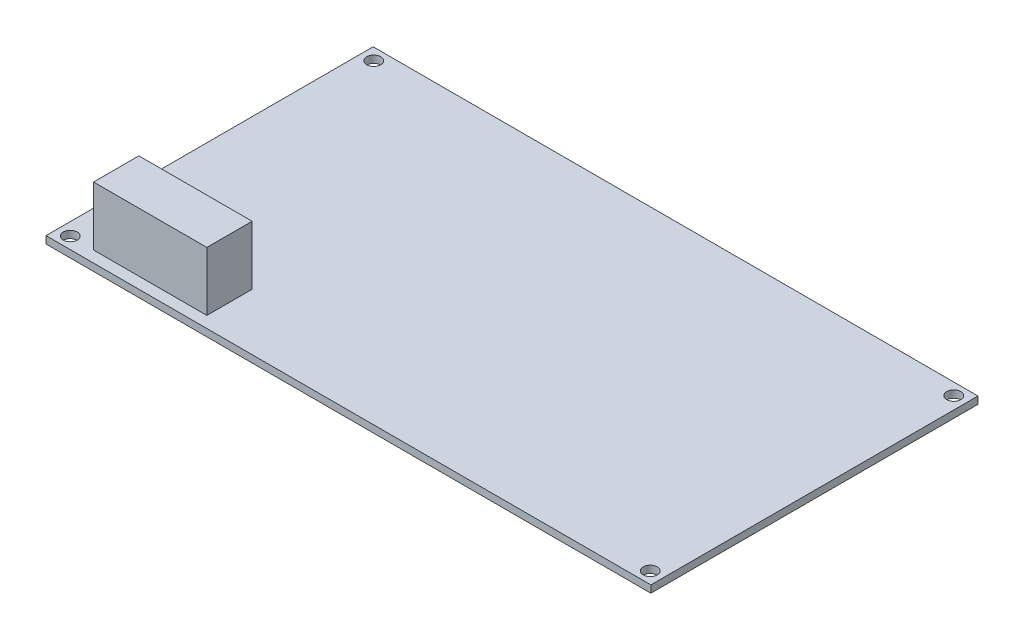
SolidWorks part; units mm, degrees
ref_plane "Front Plane" through (0, 0, 0) normal (0, 0, 1) x (1, 0, 0)
ref_plane "Top Plane" through (0, 0, 0) normal (0, 1, 0) x (1, 0, 0)
ref_plane "Right Plane" through (0, 0, 0) normal (1, 0, 0) x (0, 0, -1)
sketch "Sketch1" plane through (0, 0, 0) normal (0, 1, 0) x (1, 0, 0)
  line L0 (66.75, 72.2) -> (66.75, 69.6) construction
  line L1 (0, 0) -> (133.5, 0)
  line L2 (0, 0) -> (0, 72.2)
  line L3 (0, 72.2) -> (133.5, 72.2)
  line L4 (133.5, 0) -> (133.5, 72.2)
  line L5 (2.75, 69.6) -> (130.75, 69.6) construction
  line L6 (2.75, 69.6) -> (2.75, 2.6) construction
  line L7 (2.75, 2.6) -> (130.75, 2.6) construction
  line L8 (130.75, 69.6) -> (130.75, 2.6) construction
  line L9 (0, 36.1) -> (2.75, 36.1)
  circle A0 centre (2.75, 69.6) radius 1.55
  circle A1 centre (130.75, 69.6) radius 1.55
  circle A2 centre (130.75, 2.6) radius 1.55
  circle A3 centre (2.75, 2.6) radius 1.55
  dimension "D3" = 3.1
  dimension "D1" = 133.5
  dimension "D2" = 72.2
  dimension "D4" = 128
  dimension "D5" = 67
extrude "Boss-Extrude1" add sketch "Sketch1" along normal blind 1.6 contours L1 L4 L3 L2 A3 A2 A1 A0 region at (66.75, 0, -36.1)
sketch "Sketch2" plane through (0, 1.6, 0) normal (0, 1, 0) x (1, 0, 0)
  line L1 (8, 2.5) -> (33, 2.5)
  line L2 (8, 2.5) -> (8, 12.5)
  line L3 (8, 12.5) -> (33, 12.5)
  line L4 (33, 2.5) -> (33, 12.5)
  line L7 (0, 0) -> (133.5, 0) construction
  line L8 (0, 0) -> (0, 72.2) construction
  dimension "D1" = 10
  dimension "D2" = 25
  dimension "D3" = 2.5
  dimension "D4" = 8
extrude "Boss-Extrude2" add sketch "Sketch2" along normal blind 13
ref_plane "Plane1" through (0, 0, -36.1) normal (0, 0, 1) x (1, 0, 0)
